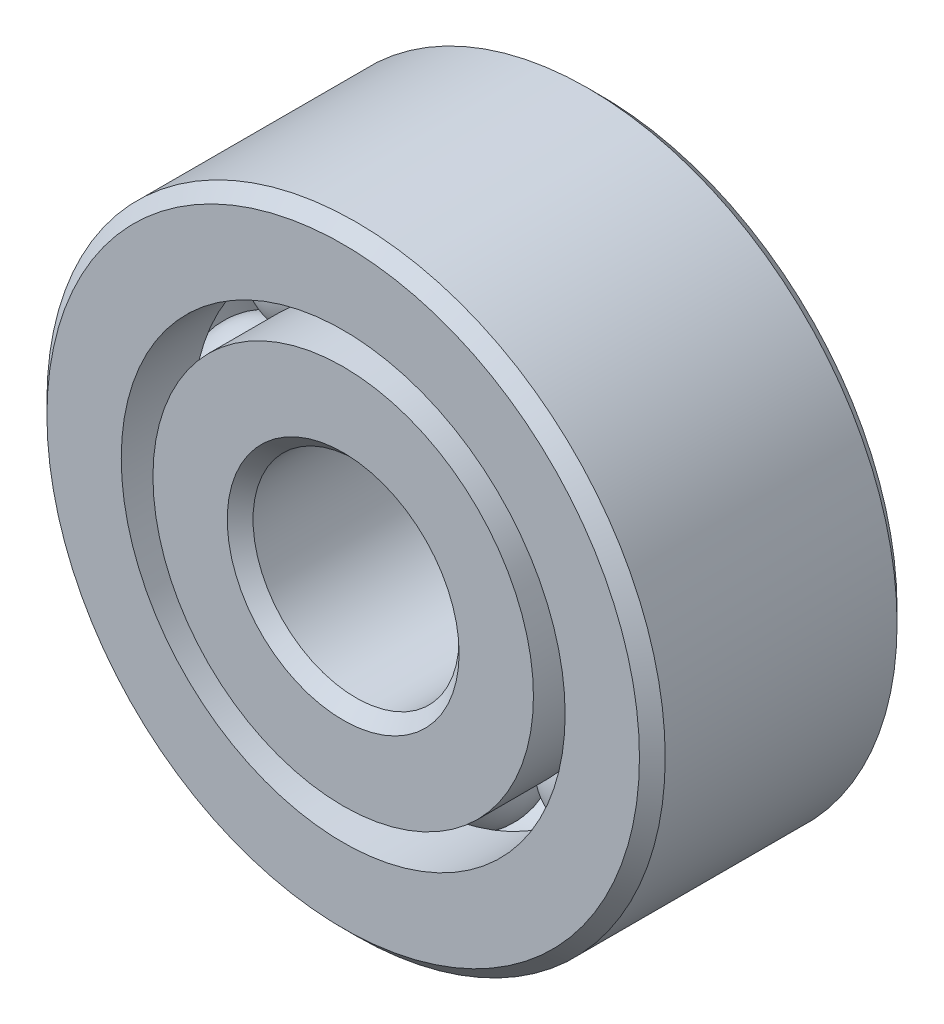
SolidWorks part; units mm, degrees
ref_plane "Front Plane" through (0, 0, 0) normal (0, 0, 1) x (1, 0, 0)
ref_plane "Top Plane" through (0, 0, 0) normal (0, 1, 0) x (1, 0, 0)
ref_plane "Right Plane" through (0, 0, 0) normal (1, 0, 0) x (0, 0, -1)
sketch "Sketch1" plane through (0, 0, 0) normal (1, 0, 0) x (0, 0, -1)
  line L0 (-1.9844, 0) -> (1.9844, 0) construction
  line L1 (0, 4.7625) -> (0, -4.7625) construction
  line L2 (1.7859, 4.7625) -> (-1.7859, 4.7625)
  line L3 (-1.7859, 4.7625) -> (-1.9844, 4.5641)
  line L4 (-1.9844, 4.5641) -> (-1.9844, 3.4192)
  line L5 (-1.9844, 3.4192) -> (-0.8819, 3.4192)
  line L6 (1.9844, 3.4192) -> (0.8819, 3.4192)
  line L7 (1.9844, 4.5641) -> (1.9844, 3.4192)
  line L8 (1.7859, 4.7625) -> (1.9844, 4.5641)
  line L9 (0, 4.7625) -> (0, 3.175) construction
  line L10 (0, 3.175) -> (0, 1.5875) construction
  arc A0 (-0.8819, 3.4192) -> (0.8819, 3.4192) centre (0, 3.175) cw
  point P14 (0, 1.5875)
  dimension "Width" = 3.9688
  dimension "OD" = 9.525
  dimension "D1" = 45
  dimension "D2" = 0.1984
  dimension "Shaft Dia" = 3.175
  dimension "D3" = 1.7639
  dimension "D4" = 0.2442
revolve "Revolve1" add sketch "Sketch1" angle 360 about L0
sketch "Sketch3" plane through (0, 0, 0) normal (1, 0, 0) x (0, 0, -1)
  line L0 (-1.9844, 2.9308) -> (-0.8819, 2.9308)
  line L1 (0, 4.7625) -> (0, -4.7625) construction
  line L2 (-1.9844, 4.5641) -> (-1.9844, 3.4192) construction
  line L3 (-1.9844, 2.9308) -> (-1.9844, 1.7859)
  line L4 (-1.7859, 4.7625) -> (-1.9844, 4.5641) construction
  line L5 (-1.9844, 1.7859) -> (-1.7859, 1.5875)
  line L6 (-1.7859, 1.5875) -> (1.7859, 1.5875)
  line L7 (1.7859, 4.7625) -> (1.7859, -4.7625) construction
  line L8 (1.7859, 1.5875) -> (1.9844, 1.7859)
  line L9 (1.9844, -4.5641) -> (1.9844, 4.5641) construction
  line L10 (1.9844, 1.7859) -> (1.9844, 2.9308)
  line L11 (1.9844, 2.9308) -> (0.8819, 2.9308)
  line L13 (1.7859, 4.7625) -> (1.9844, 4.5641) construction
  arc A0 (0.8819, 3.4192) -> (-0.8819, 3.4192) centre (0, 3.175) ccw construction
  arc A1 (0.8819, 2.9308) -> (-0.8819, 2.9308) centre (0, 3.175) cw
revolve "Revolve3" add sketch "Sketch3" angle 360 about L0
sketch "Sketch4" plane through (0, 0, 0) normal (1, 0, 0) x (0, 0, -1)
  line L0 (-0.9151, 3.175) -> (0.9151, 3.175)
  arc A2 (-0.9151, 3.175) -> (0.9151, 3.175) centre (0, 3.175) cw
  arc A3 (0.8819, 3.4192) -> (-0.8819, 3.4192) centre (0, 3.175) ccw construction
revolve "Revolve4" add sketch "Sketch4" angle 360 about L0
ref_axis "Axis1" through (0, 0, -1.9844) along (0, 0, 1)
pattern_circular "CirPattern1" count 8 every 45 about axis through (0, 0, -1.9844) along (0, 0, 1) of bodies 104
sketch "Sketch5" plane through (0, 0, 0) normal (1, 0, 0) x (0, 0, -1)
  line L0 (-1.9844, 3.4192) -> (-0.8819, 3.4192) construction
  line L1 (-1.8852, 3.4192) -> (-0.9151, 3.4192)
  line L2 (-1.8852, 3.4192) -> (-1.8852, 2.9308)
  line L3 (-1.8852, 2.9308) -> (-0.9151, 2.9308)
  line L4 (-0.9151, 3.4192) -> (-0.9151, 2.9308)
  line L5 (-1.9844, 2.9308) -> (-0.8819, 2.9308) construction
  line L6 (1.9844, 3.4192) -> (0.8819, 3.4192) construction
  line L7 (1.8852, 3.4192) -> (0.9151, 3.4192)
  line L8 (1.8852, 3.4192) -> (1.8852, 2.9308)
  line L9 (1.8852, 2.9308) -> (0.9151, 2.9308)
  line L10 (0.9151, 3.4192) -> (0.9151, 2.9308)
  line L11 (1.9844, 2.9308) -> (0.8819, 2.9308) construction
  line L12 (-1.7859, 4.7625) -> (-1.9844, 4.5641) construction
  point P18 (-1.8852, 4.6633)
revolve "Revolve5" [suppressed] add sketch "Sketch5" angle 360 about L0
equation "\"D2@Sketch1\" = \"Width@Sketch1\"*.05"
equation "\"D3@Sketch1\" = \"Width@Sketch1\"/2.25"
equation "\"D4@Sketch1\" = (((\"OD@Sketch1\"-\"Width@Sketch1\")/2)/3.25)/3.5"
equation "\"D2@CirPattern1\" = 360/\"Balls@CirPattern1\""
